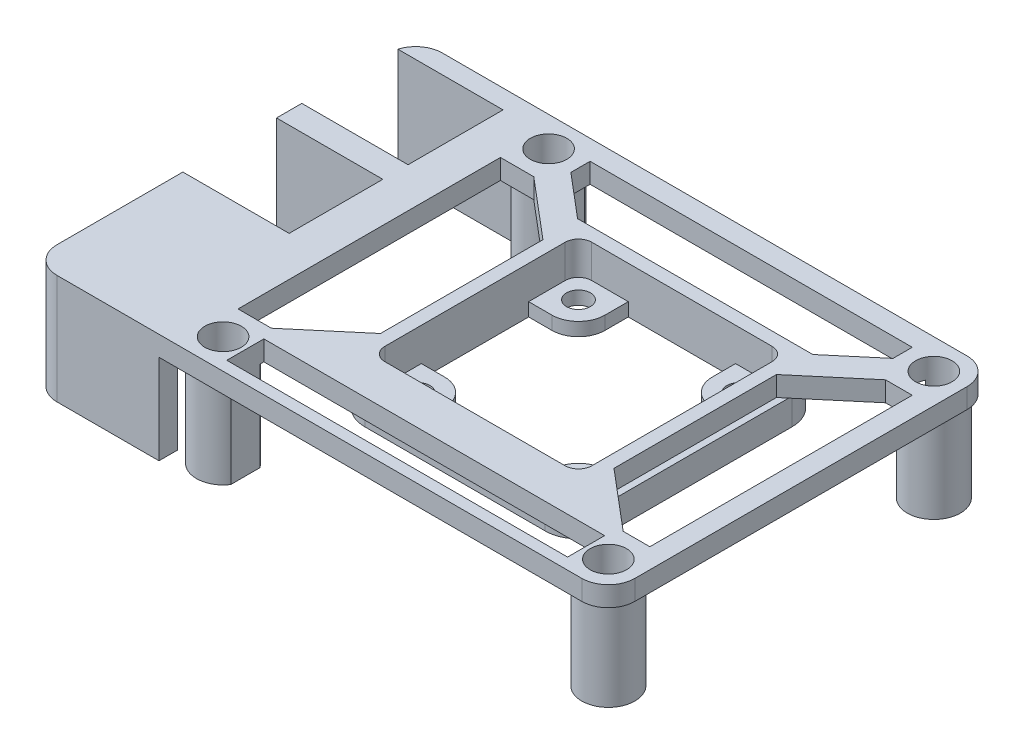
SolidWorks part; units mm, degrees
ref_plane "Front Plane" through (0, 0, 0) normal (0, 0, 1) x (1, 0, 0)
ref_plane "Top Plane" through (0, 0, 0) normal (0, 1, 0) x (1, 0, 0)
ref_plane "Right Plane" through (0, 0, 0) normal (1, 0, 0) x (0, 0, -1)
sketch "Sketch1" plane through (0, -22.49, 0) normal (0, 1, 0) x (1, 0, 0)
  circle A0 centre (42.46, 15.03) radius 4
  circle A1 centre (-15.54, 15.03) radius 4
  circle A2 centre (-15.54, -33.97) radius 4
  circle A3 centre (42.46, -33.97) radius 4
  dimension "D1" = 8
extrude "Boss-Extrude1" add sketch "Sketch1" along normal blind 16.5
sketch "Sketch2" plane through (0, -5.99, 0) normal (0, 1, 0) x (1, 0, 0)
  line L4 (-36.04, -37.47) -> (42.96, -37.47)
  line L5 (45.96, -34.47) -> (45.96, 15.53)
  line L6 (42.96, 18.53) -> (-36.04, 18.53)
  line L7 (-39.04, 15.53) -> (-39.04, -34.47)
  line L8 (-36.04, -37.47) -> (42.96, -37.47) construction
  line L9 (45.96, -34.47) -> (45.96, 15.53) construction
  line L10 (42.96, 18.53) -> (-36.04, 18.53) construction
  line L11 (-39.04, 15.53) -> (-39.04, -34.47) construction
  line L24 (-36.04, -38.47) -> (42.96, -38.47)
  line L25 (46.96, -34.47) -> (46.96, 15.53)
  line L26 (42.96, 19.53) -> (-36.04, 19.53)
  line L27 (-40.04, 15.53) -> (-40.04, -34.47)
  circle A1 centre (42.46, 15.03) radius 1.35
  circle A2 centre (42.46, 15.03) radius 1.35
  circle A3 centre (-15.54, 15.03) radius 1.35
  circle A4 centre (-15.54, 15.03) radius 1.35
  circle A5 centre (-15.54, -33.97) radius 1.35
  circle A6 centre (-15.54, -33.97) radius 1.35
  circle A7 centre (42.46, -33.97) radius 1.35
  circle A8 centre (42.46, -33.97) radius 1.35
  arc A12 (-39.04, -34.47) -> (-36.04, -37.47) centre (-36.04, -34.47) ccw
  arc A13 (42.96, -37.47) -> (45.96, -34.47) centre (42.96, -34.47) ccw
  arc A14 (45.96, 15.53) -> (42.96, 18.53) centre (42.96, 15.53) ccw
  arc A15 (-36.04, 18.53) -> (-39.04, 15.53) centre (-36.04, 15.53) ccw
  arc A16 (-39.04, -34.47) -> (-36.04, -37.47) centre (-36.04, -34.47) ccw construction
  arc A17 (42.96, -37.47) -> (45.96, -34.47) centre (42.96, -34.47) ccw construction
  arc A18 (45.96, 15.53) -> (42.96, 18.53) centre (42.96, 15.53) ccw construction
  arc A19 (-36.04, 18.53) -> (-39.04, 15.53) centre (-36.04, 15.53) ccw construction
  arc A48 (-40.04, -34.47) -> (-36.04, -38.47) centre (-36.04, -34.47) ccw
  arc A49 (42.96, -38.47) -> (46.96, -34.47) centre (42.96, -34.47) ccw
  arc A50 (46.96, 15.53) -> (42.96, 19.53) centre (42.96, 15.53) ccw
  arc A51 (-36.04, 19.53) -> (-40.04, 15.53) centre (-36.04, 15.53) ccw
  dimension "D1" = 0
  dimension "D2" = 0
  dimension "D3" = 0
  dimension "D4" = 0
  dimension "D5" = 0
  dimension "D6" = 1
extrude "Boss-Extrude2" add sketch "Sketch2" against normal blind 3
sketch "Sketch3" plane through (0, -8.99, 0) normal (0, -1, 0) x (1, 0, 0)
  line L1 (-40.04, -15.53) -> (-40.04, 34.47)
  line L2 (-36.04, 38.47) -> (-20.69, 38.47)
  line L4 (-20.69, 38.47) -> (-20.69, -19.53)
  line L6 (-20.69, -19.53) -> (-36.04, -19.53)
  line L9 (-20.69, 34.97) -> (-20.69, 19.47) construction
  line L11 (42.96, -19.53) -> (-36.04, -19.53) construction
  line L13 (-36.04, 38.47) -> (42.96, 38.47) construction
  line L14 (-40.04, -15.53) -> (-40.04, 34.47) construction
  arc A2 (-40.04, -15.53) -> (-36.04, -19.53) centre (-36.04, -15.53) ccw
  arc A3 (-36.04, 38.47) -> (-40.04, 34.47) centre (-36.04, 34.47) ccw
  arc A6 (-40.04, -15.53) -> (-36.04, -19.53) centre (-36.04, -15.53) ccw construction
  arc A7 (-36.04, 38.47) -> (-40.04, 34.47) centre (-36.04, 34.47) ccw construction
extrude "Boss-Extrude3" add sketch "Sketch3" along normal up to surface (13.5 mm away) up to face at (-19.54, -22.49, 33.97)
sketch "Sketch4" plane through (0, -5.99, 0) normal (0, 1, 0) x (1, 0, 0)
  line L1 (25.535, -21.545) -> (1.385, -21.545)
  line L2 (25.535, -21.545) -> (25.535, 2.605)
  line L3 (25.535, 2.605) -> (1.385, 2.605)
  line L4 (1.385, -21.545) -> (1.385, 2.605)
sketch "Sketch5" plane through (0, -5.99, 0) normal (0, 1, 0) x (1, 0, 0)
  line L0 (25.535, -21.545) -> (1.385, -21.545) construction
  line L1 (1.385, 2.605) -> (25.535, 2.605)
  line L2 (1.385, 2.605) -> (1.385, -21.545)
  line L3 (1.385, -21.545) -> (25.535, -21.545)
  line L4 (25.535, 2.605) -> (25.535, -21.545)
  line L5 (25.535, -21.545) -> (25.535, 2.605) construction
  line L6 (22.21, -13.97) -> (11.21, -13.97) construction
  line L7 (11.21, -8.67) -> (11.21, -19.27) construction
  line L8 (22.21, -19.27) -> (22.21, -8.67) construction
  line L9 (25.535, 2.605) -> (1.385, -21.545) construction
  line L10 (-15.54, 15.03) -> (42.46, -33.97) construction
  line L11 (-15.54, -33.97) -> (42.46, 15.03) construction
  point P10 (16.71, -13.97)
  point P23 (13.46, -9.47)
  point P24 (0, 0)
sketch "Sketch8" plane through (0, -5.99, 0) normal (0, 1, 0) x (1, 0, 0)
  line L8 (29.035, 6.105) -> (-2.115, 6.105)
  line L9 (29.035, -25.045) -> (29.035, 6.105)
  line L10 (-2.115, -25.045) -> (29.035, -25.045)
  line L11 (-2.115, 6.105) -> (-2.115, -25.045)
  line L12 (27.035, 6.105) -> (-0.115, 6.105)
  line L13 (29.035, -23.045) -> (29.035, 4.105)
  line L14 (-0.115, -25.045) -> (27.035, -25.045)
  line L15 (-2.115, 4.105) -> (-2.115, -23.045)
  arc A0 (27.035, 6.105) -> (29.035, 4.105) centre (27.035, 4.105) cw
  arc A1 (-0.115, 6.105) -> (-2.115, 4.105) centre (-0.115, 4.105) ccw
  arc A2 (-0.115, -25.045) -> (-2.115, -23.045) centre (-0.115, -23.045) cw
  arc A3 (29.035, -23.045) -> (27.035, -25.045) centre (27.035, -23.045) cw
  dimension "D2" = 2
  dimension "D1" = 3.5
extrude "Cut-Extrude1" cut sketch "Sketch8" against normal through all
sketch "Sketch9" plane through (0, -8.99, 0) normal (0, -1, 0) x (1, 0, 0)
  line L4 (-0.115, -6.105) -> (27.035, -6.105)
  line L5 (-2.115, 23.045) -> (-2.115, -4.105)
  line L6 (27.035, 25.045) -> (-0.115, 25.045)
  line L7 (29.035, -4.105) -> (29.035, 23.045)
  line L8 (-0.115, -6.105) -> (27.035, -6.105)
  line L9 (-2.115, 23.045) -> (-2.115, -4.105)
  line L10 (27.035, 25.045) -> (-0.115, 25.045)
  line L11 (29.035, -4.105) -> (29.035, 23.045)
  line L12 (32.035, -4.105) -> (32.035, 23.045)
  line L13 (27.035, 28.045) -> (-0.115, 28.045)
  line L14 (-5.115, 23.045) -> (-5.115, -4.105)
  line L15 (-0.115, -9.105) -> (27.035, -9.105)
  arc A4 (-2.115, -4.105) -> (-0.115, -6.105) centre (-0.115, -4.105) ccw
  arc A5 (-0.115, 25.045) -> (-2.115, 23.045) centre (-0.115, 23.045) ccw
  arc A6 (29.035, 23.045) -> (27.035, 25.045) centre (27.035, 23.045) ccw
  arc A7 (27.035, -6.105) -> (29.035, -4.105) centre (27.035, -4.105) ccw
  arc A8 (-2.115, -4.105) -> (-0.115, -6.105) centre (-0.115, -4.105) ccw
  arc A9 (-0.115, 25.045) -> (-2.115, 23.045) centre (-0.115, 23.045) ccw
  arc A10 (29.035, 23.045) -> (27.035, 25.045) centre (27.035, 23.045) ccw
  arc A11 (27.035, -6.105) -> (29.035, -4.105) centre (27.035, -4.105) ccw
  arc A12 (32.035, 23.045) -> (27.035, 28.045) centre (27.035, 23.045) ccw
  arc A13 (-0.115, 28.045) -> (-5.115, 23.045) centre (-0.115, 23.045) ccw
  arc A14 (-5.115, -4.105) -> (-0.115, -9.105) centre (-0.115, -4.105) ccw
  arc A15 (27.035, -9.105) -> (32.035, -4.105) centre (27.035, -4.105) ccw
  dimension "D1" = 0
  dimension "D3" = 3
extrude "Boss-Extrude4" add sketch "Sketch9" along normal offset from surface (4 mm away) 2 offset beyond the face yes
sketch "Sketch10" plane through (0, -12.99, 0) normal (0, -1, 0) x (1, 0, 0)
  line L0 (29.035, 17.545) -> (25.535, 17.545)
  line L1 (29.035, 23.045) -> (29.035, -4.105) construction
  line L2 (21.535, 21.545) -> (21.535, 25.045)
  line L3 (-0.115, 25.045) -> (27.035, 25.045) construction
  line L4 (27.035, -6.105) -> (-0.115, -6.105) construction
  line L5 (-2.115, -4.105) -> (-2.115, 23.045) construction
  line L6 (27.035, -6.105) -> (21.535, -6.105)
  line L7 (-2.115, -4.105) -> (-2.115, 1.395)
  line L8 (-0.115, 25.045) -> (5.385, 25.045)
  line L9 (29.035, 23.045) -> (29.035, 17.545)
  line L10 (5.385, 21.545) -> (5.385, 25.045)
  line L11 (1.385, 17.545) -> (-2.115, 17.545)
  line L12 (1.385, 1.395) -> (-2.115, 1.395)
  line L13 (5.385, -2.605) -> (5.385, -6.105)
  line L14 (25.535, 1.395) -> (29.035, 1.395)
  line L15 (21.535, -2.605) -> (21.535, -6.105)
  line L16 (-2.115, 17.545) -> (-2.115, 23.045)
  line L17 (5.385, -6.105) -> (-0.115, -6.105)
  line L18 (29.035, 1.395) -> (29.035, -4.105)
  line L19 (21.535, 25.045) -> (27.035, 25.045)
  arc A0 (21.535, 21.545) -> (25.535, 17.545) centre (25.535, 21.545) ccw
  arc A1 (1.385, 17.545) -> (5.385, 21.545) centre (1.385, 21.545) ccw
  arc A2 (5.385, -2.605) -> (1.385, 1.395) centre (1.385, -2.605) ccw
  arc A3 (25.535, 1.395) -> (21.535, -2.605) centre (25.535, -2.605) ccw
  arc A4 (27.035, -6.105) -> (29.035, -4.105) centre (27.035, -4.105) ccw construction
  arc A5 (-2.115, -4.105) -> (-0.115, -6.105) centre (-0.115, -4.105) ccw construction
  arc A6 (-0.115, 25.045) -> (-2.115, 23.045) centre (-0.115, 23.045) ccw construction
  arc A7 (29.035, 23.045) -> (27.035, 25.045) centre (27.035, 23.045) ccw construction
  arc A8 (27.035, -6.105) -> (29.035, -4.105) centre (27.035, -4.105) ccw
  arc A9 (-2.115, -4.105) -> (-0.115, -6.105) centre (-0.115, -4.105) ccw
  arc A10 (-0.115, 25.045) -> (-2.115, 23.045) centre (-0.115, 23.045) ccw
  arc A11 (29.035, 23.045) -> (27.035, 25.045) centre (27.035, 23.045) ccw
  dimension "D1" = 4
extrude "Boss-Extrude5" add sketch "Sketch10" against normal up to surface (2 mm away)
hole_wizard "M3 Clearance Hole1" positions "Sketch6" profile "Sketch7" hole size "M3" standard "ANSI Metric" end condition through all
sketch "Sketch6" plane through (0, -5.99, 0) normal (0, 1, 0) x (1, 0, 0)
  point P0 (25.535, -21.545)
  point P3 (1.385, -21.545)
  point P6 (1.385, 2.605)
  point P9 (25.535, 2.605)
sketch "Sketch7" plane through (25.535, -5.99, 21.545) normal (1, 0, 0) x (0, 0, 1)
  line L0 (0, 0) -> (0, 16.5)
  line L1 (0, 16.5) -> (1.8, 16.5)
  line L2 (1.8, 16.5) -> (1.8, 0)
  line L5 (1.8, 0) -> (0, 0)
  line L11 (0, -6.35) -> (0, 107.95) construction
  dimension "Thru Hole Dia." = 3.6
  dimension "Thru Hole Depth" = 16.5
sketch "Sketch11" plane through (0, -5.99, 0) normal (0, 1, 0) x (1, 0, 0)
  line L0 (-12.19, -36.76) -> (39.11, -36.76)
  line L1 (39.11, -36.76) -> (39.11, -31.18)
  line L2 (39.11, -31.18) -> (-12.19, -31.18)
  line L3 (-12.19, -31.18) -> (-12.19, -36.76)
  line L4 (-11.94, -36.51) -> (38.86, -36.51)
  line L5 (38.86, -36.51) -> (38.86, -31.43)
  line L6 (38.86, -31.43) -> (-11.94, -31.43)
  line L7 (-11.94, -31.43) -> (-11.94, -36.51)
  line L8 (-11.94, -36.51) -> (38.86, -36.51) construction
  line L9 (38.86, -36.51) -> (38.86, -31.43) construction
  line L10 (38.86, -31.43) -> (-11.94, -31.43) construction
  line L11 (-11.94, -31.43) -> (-11.94, -36.51) construction
  dimension "D1" = 0
  dimension "D2" = 0.25
extrude "Cut-Extrude2" cut sketch "Sketch11" against normal through all
sketch "Sketch12" plane through (-40.04, 0, 0) normal (-1, 0, 0) x (0, 0, 1)
  line L28 (1.42, -24.59) -> (15.52, -24.59)
  line L29 (15.52, -24.59) -> (15.52, -6.49)
  line L30 (15.52, -6.49) -> (1.42, -6.49) construction
  line L31 (1.42, -6.49) -> (1.42, -24.59)
  line L32 (1.92, -24.09) -> (15.02, -24.09)
  line L33 (15.02, -24.09) -> (15.02, -6.99)
  line L34 (15.02, -6.99) -> (1.92, -6.99)
  line L35 (1.92, -6.99) -> (1.92, -24.09)
  line L36 (1.92, -24.09) -> (15.02, -24.09) construction
  line L37 (15.02, -24.09) -> (15.02, -6.99) construction
  line L38 (15.02, -6.99) -> (1.92, -6.99) construction
  line L39 (1.92, -6.99) -> (1.92, -24.09) construction
  line L40 (-16.18, -24.09) -> (-2.88, -24.09)
  line L41 (-2.88, -24.09) -> (-2.88, -6.99)
  line L42 (-2.88, -6.99) -> (-16.18, -6.99)
  line L43 (-16.18, -6.99) -> (-16.18, -24.09)
  line L44 (-16.18, -24.09) -> (-2.88, -24.09) construction
  line L45 (-2.88, -24.09) -> (-2.88, -6.99) construction
  line L46 (-2.88, -6.99) -> (-16.18, -6.99) construction
  line L47 (-16.18, -6.99) -> (-16.18, -24.09) construction
  line L48 (19.27, -9.19) -> (19.27, -24.09)
  line L49 (34.97, -8.99) -> (19.47, -8.99)
  line L50 (35.17, -24.09) -> (35.17, -9.19)
  line L51 (19.27, -24.09) -> (35.17, -24.09)
  line L52 (19.27, -9.19) -> (19.27, -24.09) construction
  line L53 (34.97, -8.99) -> (19.47, -8.99) construction
  line L54 (35.17, -24.09) -> (35.17, -9.19) construction
  line L55 (19.27, -24.09) -> (35.17, -24.09) construction
  line L56 (-16.68, -24.59) -> (-2.38, -24.59)
  line L57 (-2.38, -24.59) -> (-2.38, -6.49)
  line L58 (-2.38, -6.49) -> (-16.68, -6.49) construction
  line L59 (-16.68, -6.49) -> (-16.68, -24.59)
  line L60 (18.77, -9.19) -> (18.77, -24.59)
  line L61 (18.77, -24.59) -> (35.67, -24.59)
  line L62 (35.67, -24.59) -> (35.67, -9.19)
  line L63 (34.97, -8.49) -> (19.47, -8.49)
  line L64 (-16.68, -6.49) -> (-16.68, -5.99)
  line L66 (-16.68, -5.99) -> (-2.38, -5.99)
  line L68 (-2.38, -5.99) -> (-2.38, -6.49)
  line L69 (1.42, -6.49) -> (1.42, -5.99)
  line L70 (1.42, -5.99) -> (15.52, -5.99)
  line L71 (-2.605, -5.99) -> (21.545, -5.99) construction
  line L72 (15.52, -5.99) -> (15.52, -6.49)
  line L88 (-15.53, -5.99) -> (34.47, -5.99) construction
  arc A0 (35.67, -9.19) -> (34.97, -8.49) centre (34.97, -9.19) ccw
  arc A1 (19.47, -8.49) -> (18.77, -9.19) centre (19.47, -9.19) ccw
  arc A2 (19.47, -8.99) -> (19.27, -9.19) centre (19.47, -9.19) ccw
  arc A3 (35.17, -9.19) -> (34.97, -8.99) centre (34.97, -9.19) ccw
  arc A4 (19.47, -8.99) -> (19.27, -9.19) centre (19.47, -9.19) ccw construction
  arc A5 (35.17, -9.19) -> (34.97, -8.99) centre (34.97, -9.19) ccw construction
  dimension "D1" = 0
  dimension "D2" = 0
  dimension "D3" = 0
  dimension "D4" = 0.5
extrude "Cut-Extrude3" cut sketch "Sketch12" against normal blind 16 contours L59 L56 L57 L68 L66 L64 | L31 L28 L29 L72 L70 L69
extrude "Cut-Extrude4" cut sketch "Sketch12<3>" against normal blind 20 contours L60 L61 L62 A0 L63 A1
sketch "Sketch12<3>" plane through (-40.04, 0, 0) normal (-1, 0, 0) x (0, 0, 1) same geometry as "Sketch12"
sketch "Sketch13" plane through (-20.69, 0, 0) normal (1, 0, 0) x (0, 0, -1)
  line L4 (19.53, -8.99) -> (-18.7992, -8.99)
  line L5 (-18.77, -9.19) -> (-18.77, -22.49)
  line L6 (-18.77, -22.49) -> (19.53, -22.49)
  line L10 (-18.77, -22.49) -> (19.53, -22.49)
  line L15 (-18.77, -9.19) -> (-18.77, -22.49)
  line L17 (19.53, -22.49) -> (19.53, -8.99)
  line L18 (19.53, -22.49) -> (19.53, -8.99)
  line L19 (19.53, -8.99) -> (-18.7992, -8.99)
  arc A1 (-18.77, -9.19) -> (-18.7992, -8.99) centre (-19.47, -9.19) ccw
  arc A4 (-18.77, -9.19) -> (-18.7992, -8.99) centre (-19.47, -9.19) ccw
  dimension "D1" = 0
extrude "Cut-Extrude5" cut sketch "Sketch13" against normal offset from surface (1.35 mm away) 2 up to face at (-24.04, -14.24, -9.53)
sketch "Sketch15" plane through (0, 0, 18.77) normal (0, 0, 1) x (1, 0, 0)
  line L0 (-37.04, -22.49) -> (-22.04, -12.19)
  line L1 (-22.04, -22.49) -> (-40.04, -22.49) construction
  line L2 (-22.04, -22.49) -> (-22.04, -9.19) construction
  line L3 (-22.04, -12.19) -> (-22.04, -22.49)
  line L4 (-22.04, -22.49) -> (-37.04, -22.49)
  line L5 (-40.04, -22.49) -> (-37.04, -22.49) construction
  line L6 (-22.04, -12.19) -> (-22.04, -9.19) construction
  dimension "D1" = 3
extrude "Cut-Extrude6" cut sketch "Sketch15" against normal up to surface (35.45 mm away) up to face at (-31.9556, -14.24, -16.68)
hole_wizard "CBORE for M2.5 SHCS1" positions "Sketch16" profile "Sketch17" counterbore size "M2.5" standard "ANSI Metric" end condition through all
sketch "Sketch16" plane through (0, -5.99, 0) normal (0, 1, 0) x (1, 0, 0)
  point P0 (-15.54, -33.97)
  point P3 (-15.54, 15.03)
  point P6 (42.46, 15.03)
  point P9 (42.46, -33.97)
sketch "Sketch17" plane through (-15.54, -5.99, 33.97) normal (1, 0, 0) x (0, 0, 1)
  line L0 (0, 0) -> (0, 16.5)
  line L1 (0, 16.5) -> (1.45, 16.5)
  line L3 (1.45, 16.5) -> (1.45, 2.5)
  line L4 (1.45, 2.5) -> (2.75, 2.5)
  line L5 (2.75, 2.5) -> (2.75, 0)
  line L7 (2.75, 0) -> (0, 0)
  line L11 (0, -6.35) -> (0, 107.95) construction
  dimension "Thru Hole Dia." = 2.9
  dimension "Thru Hole Depth" = 16.5
  dimension "C'Bore Dia." = 5.5
  dimension "C'Bore Depth" = 2.5
sketch "Sketch18" plane through (0, -8.49, 0) normal (0, 1, 0) x (1, 0, 0)
  circle A0 centre (-15.54, 15.03) radius 2.75 construction
  circle A1 centre (42.46, 15.03) radius 2.75
  circle A2 centre (42.46, 15.03) radius 2.75
  circle A3 centre (-15.54, -33.97) radius 2.75 construction
  circle A4 centre (42.46, -33.97) radius 2.75 construction
  circle A5 centre (-15.54, 15.03) radius 2.75
  circle A6 centre (-15.54, -33.97) radius 2.75
  circle A7 centre (42.46, -33.97) radius 2.75
  dimension "D1" = 0
extrude "Cut-Extrude7" cut sketch "Sketch18" against normal offset from surface (8.6 mm away) 7
sketch "Sketch19" plane through (0, -8.99, 0) normal (0, -1, 0) x (-1, 0, 0)
  line L0 (-42.96, 19.53) -> (22.04, 19.53) construction
  line L1 (-39.98, 19.53) -> (12.04, 19.53)
  line L2 (-39.98, 19.53) -> (-39.98, 9.53)
  line L3 (-39.98, 9.53) -> (12.04, 9.53)
  line L4 (12.04, 19.53) -> (12.04, 9.53)
  line L5 (11.04, 18.53) -> (5.04, 18.53) construction
  line L6 (11.04, 18.53) -> (5.04, 18.53) construction
  line L7 (-37.93, 18.53) -> (-39.23, 18.53) construction
  line L8 (-37.93, 18.53) -> (-39.23, 18.53) construction
  dimension "D1" = 10
  dimension "D2" = 1
  dimension "D3" = 0.75
extrude "Cut-Extrude8" cut sketch "Sketch19" along normal through all
sketch "Sketch20" [suppressed] plane through (0, -5.99, 0) normal (0, 1, 0) x (1, 0, 0)
  line L0 (-15.54, 11.5659) -> (-13.54, 15.03) construction
  line L1 (-13.54, 15.03) -> (-9.54, 15.03) construction
  line L2 (-9.54, 15.03) -> (-11.54, 11.5659) construction
  line L3 (-11.54, 11.5659) -> (-15.54, 11.5659) construction
  line L4 (-15.54, 11.5659) -> (-15.54, 15.03) construction
  line L5 (-15.54, 15.03) -> (-13.54, 15.03) construction
  circle A0 centre (-13.54, 15.03) radius 1.5
  circle A1 centre (-9.54, 15.03) radius 1.5
  circle A2 centre (-15.54, 11.5659) radius 1.5
  circle A3 centre (-11.54, 11.5659) radius 1.5
  point P9 (-15.54, 15.03)
  dimension "D1" = 60
  dimension "D2" = 3
  dimension "D3" = 4
sketch "Sketch21" [suppressed] plane through (0, -5.99, 0) normal (0, 1, 0) x (1, 0, 0)
  line L0 (-9.54, 15.03) -> (-5.54, 15.03) construction
  line L1 (-11.54, 11.5659) -> (-13.54, 8.1018) construction
  line L2 (-9.54, 15.03) -> (-11.54, 11.5659) construction
  line L3 (-13.54, 15.03) -> (-9.54, 15.03) construction
  circle A0 centre (-3.54, 11.5659) radius 1.5
  circle A1 centre (-11.54, 11.5659) radius 1.5
  circle A2 centre (-11.54, 11.5659) radius 1.5
  circle A3 centre (-15.54, 11.5659) radius 1.5
  circle A4 centre (-15.54, 11.5659) radius 1.5
  circle A5 centre (-9.54, 15.03) radius 1.5
  circle A6 centre (-9.54, 15.03) radius 1.5
  circle A7 centre (-13.54, 15.03) radius 1.5
  circle A8 centre (-13.54, 15.03) radius 1.5
  circle A9 centre (-7.54, 11.5659) radius 1.5
  circle A10 centre (-1.54, 15.03) radius 1.5
  circle A11 centre (-5.54, 15.03) radius 1.5
  circle A12 centre (4.46, 11.5659) radius 1.5
  circle A13 centre (0.46, 11.5659) radius 1.5
  circle A14 centre (6.46, 15.03) radius 1.5
  circle A15 centre (2.46, 15.03) radius 1.5
  circle A16 centre (12.46, 11.5659) radius 1.5
  circle A17 centre (8.46, 11.5659) radius 1.5
  circle A18 centre (14.46, 15.03) radius 1.5
  circle A19 centre (10.46, 15.03) radius 1.5
  circle A20 centre (20.46, 11.5659) radius 1.5
  circle A21 centre (16.46, 11.5659) radius 1.5
  circle A22 centre (22.46, 15.03) radius 1.5
  circle A23 centre (18.46, 15.03) radius 1.5
  circle A24 centre (28.46, 11.5659) radius 1.5
  circle A25 centre (24.46, 11.5659) radius 1.5
  circle A26 centre (30.46, 15.03) radius 1.5
  circle A27 centre (26.46, 15.03) radius 1.5
  circle A28 centre (36.46, 11.5659) radius 1.5
  circle A29 centre (32.46, 11.5659) radius 1.5
  circle A30 centre (38.46, 15.03) radius 1.5
  circle A31 centre (34.46, 15.03) radius 1.5
  circle A32 centre (44.46, 11.5659) radius 1.5
  circle A33 centre (40.46, 11.5659) radius 1.5
  circle A34 centre (46.46, 15.03) radius 1.5
  circle A35 centre (42.46, 15.03) radius 1.5
  circle A36 centre (-3.54, 4.6377) radius 1.5
  circle A37 centre (-7.54, 4.6377) radius 1.5
  circle A38 centre (-1.54, 8.1018) radius 1.5
  circle A39 centre (-5.54, 8.1018) radius 1.5
  circle A40 centre (4.46, 4.6377) radius 1.5
  circle A41 centre (0.46, 4.6377) radius 1.5
  circle A42 centre (6.46, 8.1018) radius 1.5
  circle A43 centre (2.46, 8.1018) radius 1.5
  circle A44 centre (12.46, 4.6377) radius 1.5
  circle A45 centre (8.46, 4.6377) radius 1.5
  circle A46 centre (14.46, 8.1018) radius 1.5
  circle A47 centre (10.46, 8.1018) radius 1.5
  circle A48 centre (20.46, 4.6377) radius 1.5
  circle A49 centre (16.46, 4.6377) radius 1.5
  circle A50 centre (22.46, 8.1018) radius 1.5
  circle A51 centre (18.46, 8.1018) radius 1.5
  circle A52 centre (28.46, 4.6377) radius 1.5
  circle A53 centre (24.46, 4.6377) radius 1.5
  circle A54 centre (30.46, 8.1018) radius 1.5
  circle A55 centre (26.46, 8.1018) radius 1.5
  circle A56 centre (36.46, 4.6377) radius 1.5
  circle A57 centre (32.46, 4.6377) radius 1.5
  circle A58 centre (38.46, 8.1018) radius 1.5
  circle A59 centre (34.46, 8.1018) radius 1.5
  circle A60 centre (44.46, 4.6377) radius 1.5
  circle A61 centre (40.46, 4.6377) radius 1.5
  circle A62 centre (46.46, 8.1018) radius 1.5
  circle A63 centre (42.46, 8.1018) radius 1.5
  circle A64 centre (-3.54, -2.2905) radius 1.5
  circle A65 centre (-7.54, -2.2905) radius 1.5
  circle A66 centre (-1.54, 1.1736) radius 1.5
  circle A67 centre (-5.54, 1.1736) radius 1.5
  circle A68 centre (4.46, -2.2905) radius 1.5
  circle A69 centre (0.46, -2.2905) radius 1.5
  circle A70 centre (6.46, 1.1736) radius 1.5
  circle A71 centre (2.46, 1.1736) radius 1.5
  circle A72 centre (12.46, -2.2905) radius 1.5
  circle A73 centre (8.46, -2.2905) radius 1.5
  circle A74 centre (14.46, 1.1736) radius 1.5
  circle A75 centre (10.46, 1.1736) radius 1.5
  circle A76 centre (20.46, -2.2905) radius 1.5
  circle A77 centre (16.46, -2.2905) radius 1.5
  circle A78 centre (22.46, 1.1736) radius 1.5
  circle A79 centre (18.46, 1.1736) radius 1.5
  circle A80 centre (28.46, -2.2905) radius 1.5
  circle A81 centre (24.46, -2.2905) radius 1.5
  circle A82 centre (30.46, 1.1736) radius 1.5
  circle A83 centre (26.46, 1.1736) radius 1.5
  circle A84 centre (36.46, -2.2905) radius 1.5
  circle A85 centre (32.46, -2.2905) radius 1.5
  circle A86 centre (38.46, 1.1736) radius 1.5
  circle A87 centre (34.46, 1.1736) radius 1.5
  circle A88 centre (44.46, -2.2905) radius 1.5
  circle A89 centre (40.46, -2.2905) radius 1.5
  circle A90 centre (46.46, 1.1736) radius 1.5
  circle A91 centre (42.46, 1.1736) radius 1.5
  circle A92 centre (-3.54, -9.2187) radius 1.5
  circle A93 centre (-7.54, -9.2187) radius 1.5
  circle A94 centre (-1.54, -5.7546) radius 1.5
  circle A95 centre (-5.54, -5.7546) radius 1.5
  circle A96 centre (4.46, -9.2187) radius 1.5
  circle A97 centre (0.46, -9.2187) radius 1.5
  circle A98 centre (6.46, -5.7546) radius 1.5
  circle A99 centre (2.46, -5.7546) radius 1.5
  circle A100 centre (12.46, -9.2187) radius 1.5
  circle A101 centre (8.46, -9.2187) radius 1.5
  circle A102 centre (14.46, -5.7546) radius 1.5
  circle A103 centre (10.46, -5.7546) radius 1.5
  circle A104 centre (20.46, -9.2187) radius 1.5
  circle A105 centre (16.46, -9.2187) radius 1.5
  circle A106 centre (22.46, -5.7546) radius 1.5
  circle A107 centre (18.46, -5.7546) radius 1.5
  circle A108 centre (28.46, -9.2187) radius 1.5
  circle A109 centre (24.46, -9.2187) radius 1.5
  circle A110 centre (30.46, -5.7546) radius 1.5
  circle A111 centre (26.46, -5.7546) radius 1.5
  circle A112 centre (36.46, -9.2187) radius 1.5
  circle A113 centre (32.46, -9.2187) radius 1.5
  circle A114 centre (38.46, -5.7546) radius 1.5
  circle A115 centre (34.46, -5.7546) radius 1.5
  circle A116 centre (44.46, -9.2187) radius 1.5
  circle A117 centre (40.46, -9.2187) radius 1.5
  circle A118 centre (46.46, -5.7546) radius 1.5
  circle A119 centre (42.46, -5.7546) radius 1.5
  circle A120 centre (-3.54, -16.1469) radius 1.5
  circle A121 centre (-7.54, -16.1469) radius 1.5
  circle A122 centre (-1.54, -12.6828) radius 1.5
  circle A123 centre (-5.54, -12.6828) radius 1.5
  circle A124 centre (4.46, -16.1469) radius 1.5
  circle A125 centre (0.46, -16.1469) radius 1.5
  circle A126 centre (6.46, -12.6828) radius 1.5
  circle A127 centre (2.46, -12.6828) radius 1.5
  circle A128 centre (12.46, -16.1469) radius 1.5
  circle A129 centre (8.46, -16.1469) radius 1.5
  circle A130 centre (14.46, -12.6828) radius 1.5
  circle A131 centre (10.46, -12.6828) radius 1.5
  circle A132 centre (20.46, -16.1469) radius 1.5
  circle A133 centre (16.46, -16.1469) radius 1.5
  circle A134 centre (22.46, -12.6828) radius 1.5
  circle A135 centre (18.46, -12.6828) radius 1.5
  circle A136 centre (28.46, -16.1469) radius 1.5
  circle A137 centre (24.46, -16.1469) radius 1.5
  circle A138 centre (30.46, -12.6828) radius 1.5
  circle A139 centre (26.46, -12.6828) radius 1.5
  circle A140 centre (36.46, -16.1469) radius 1.5
  circle A141 centre (32.46, -16.1469) radius 1.5
  circle A142 centre (38.46, -12.6828) radius 1.5
  circle A143 centre (34.46, -12.6828) radius 1.5
  circle A144 centre (44.46, -16.1469) radius 1.5
  circle A145 centre (40.46, -16.1469) radius 1.5
  circle A146 centre (46.46, -12.6828) radius 1.5
  circle A147 centre (42.46, -12.6828) radius 1.5
  circle A148 centre (-3.54, -23.0751) radius 1.5
  circle A149 centre (-7.54, -23.0751) radius 1.5
  circle A150 centre (-1.54, -19.611) radius 1.5
  circle A151 centre (-5.54, -19.611) radius 1.5
  circle A152 centre (4.46, -23.0751) radius 1.5
  circle A153 centre (0.46, -23.0751) radius 1.5
  circle A154 centre (6.46, -19.611) radius 1.5
  circle A155 centre (2.46, -19.611) radius 1.5
  circle A156 centre (12.46, -23.0751) radius 1.5
  circle A157 centre (8.46, -23.0751) radius 1.5
  circle A158 centre (14.46, -19.611) radius 1.5
  circle A159 centre (10.46, -19.611) radius 1.5
  circle A160 centre (20.46, -23.0751) radius 1.5
  circle A161 centre (16.46, -23.0751) radius 1.5
  circle A162 centre (22.46, -19.611) radius 1.5
  circle A163 centre (18.46, -19.611) radius 1.5
  circle A164 centre (28.46, -23.0751) radius 1.5
  circle A165 centre (24.46, -23.0751) radius 1.5
  circle A166 centre (30.46, -19.611) radius 1.5
  circle A167 centre (26.46, -19.611) radius 1.5
  circle A168 centre (36.46, -23.0751) radius 1.5
  circle A169 centre (32.46, -23.0751) radius 1.5
  circle A170 centre (38.46, -19.611) radius 1.5
  circle A171 centre (34.46, -19.611) radius 1.5
  circle A172 centre (44.46, -23.0751) radius 1.5
  circle A173 centre (40.46, -23.0751) radius 1.5
  circle A174 centre (46.46, -19.611) radius 1.5
  circle A175 centre (42.46, -19.611) radius 1.5
  circle A176 centre (-3.54, -30.0033) radius 1.5
  circle A177 centre (-7.54, -30.0033) radius 1.5
  circle A178 centre (-1.54, -26.5392) radius 1.5
  circle A179 centre (-5.54, -26.5392) radius 1.5
  circle A180 centre (4.46, -30.0033) radius 1.5
  circle A181 centre (0.46, -30.0033) radius 1.5
  circle A182 centre (6.46, -26.5392) radius 1.5
  circle A183 centre (2.46, -26.5392) radius 1.5
  circle A184 centre (12.46, -30.0033) radius 1.5
  circle A185 centre (8.46, -30.0033) radius 1.5
  circle A186 centre (14.46, -26.5392) radius 1.5
  circle A187 centre (10.46, -26.5392) radius 1.5
  circle A188 centre (20.46, -30.0033) radius 1.5
  circle A189 centre (16.46, -30.0033) radius 1.5
  circle A190 centre (22.46, -26.5392) radius 1.5
  circle A191 centre (18.46, -26.5392) radius 1.5
  circle A192 centre (28.46, -30.0033) radius 1.5
  circle A193 centre (24.46, -30.0033) radius 1.5
  circle A194 centre (30.46, -26.5392) radius 1.5
  circle A195 centre (26.46, -26.5392) radius 1.5
  circle A196 centre (36.46, -30.0033) radius 1.5
  circle A197 centre (32.46, -30.0033) radius 1.5
  circle A198 centre (38.46, -26.5392) radius 1.5
  circle A199 centre (34.46, -26.5392) radius 1.5
  circle A200 centre (44.46, -30.0033) radius 1.5
  circle A201 centre (40.46, -30.0033) radius 1.5
  circle A202 centre (46.46, -26.5392) radius 1.5
  circle A203 centre (42.46, -26.5392) radius 1.5
  circle A204 centre (-3.54, -36.9315) radius 1.5
  circle A205 centre (-7.54, -36.9315) radius 1.5
  circle A206 centre (-1.54, -33.4674) radius 1.5
  circle A207 centre (-5.54, -33.4674) radius 1.5
  circle A208 centre (4.46, -36.9315) radius 1.5
  circle A209 centre (0.46, -36.9315) radius 1.5
  circle A210 centre (6.46, -33.4674) radius 1.5
  circle A211 centre (2.46, -33.4674) radius 1.5
  circle A212 centre (12.46, -36.9315) radius 1.5
  circle A213 centre (8.46, -36.9315) radius 1.5
  circle A214 centre (14.46, -33.4674) radius 1.5
  circle A215 centre (10.46, -33.4674) radius 1.5
  circle A216 centre (20.46, -36.9315) radius 1.5
  circle A217 centre (16.46, -36.9315) radius 1.5
  circle A218 centre (22.46, -33.4674) radius 1.5
  circle A219 centre (18.46, -33.4674) radius 1.5
  circle A220 centre (28.46, -36.9315) radius 1.5
  circle A221 centre (24.46, -36.9315) radius 1.5
  circle A222 centre (30.46, -33.4674) radius 1.5
  circle A223 centre (26.46, -33.4674) radius 1.5
  circle A224 centre (36.46, -36.9315) radius 1.5
  circle A225 centre (32.46, -36.9315) radius 1.5
  circle A226 centre (38.46, -33.4674) radius 1.5
  circle A227 centre (34.46, -33.4674) radius 1.5
  circle A228 centre (44.46, -36.9315) radius 1.5
  circle A229 centre (40.46, -36.9315) radius 1.5
  circle A230 centre (46.46, -33.4674) radius 1.5
  circle A231 centre (42.46, -33.4674) radius 1.5
  circle A232 centre (-11.54, 4.6377) radius 1.5
  circle A233 centre (-15.54, 4.6377) radius 1.5
  circle A234 centre (-9.54, 8.1018) radius 1.5
  circle A235 centre (-13.54, 8.1018) radius 1.5
  circle A236 centre (-11.54, -2.2905) radius 1.5
  circle A237 centre (-15.54, -2.2905) radius 1.5
  circle A238 centre (-9.54, 1.1736) radius 1.5
  circle A239 centre (-13.54, 1.1736) radius 1.5
  circle A240 centre (-11.54, -9.2187) radius 1.5
  circle A241 centre (-15.54, -9.2187) radius 1.5
  circle A242 centre (-9.54, -5.7546) radius 1.5
  circle A243 centre (-13.54, -5.7546) radius 1.5
  circle A244 centre (-11.54, -16.1469) radius 1.5
  circle A245 centre (-15.54, -16.1469) radius 1.5
  circle A246 centre (-9.54, -12.6828) radius 1.5
  circle A247 centre (-13.54, -12.6828) radius 1.5
  circle A248 centre (-11.54, -23.0751) radius 1.5
  circle A249 centre (-15.54, -23.0751) radius 1.5
  circle A250 centre (-9.54, -19.611) radius 1.5
  circle A251 centre (-13.54, -19.611) radius 1.5
  circle A252 centre (-11.54, -30.0033) radius 1.5
  circle A253 centre (-15.54, -30.0033) radius 1.5
  circle A254 centre (-9.54, -26.5392) radius 1.5
  circle A255 centre (-13.54, -26.5392) radius 1.5
  circle A256 centre (-11.54, -36.9315) radius 1.5
  circle A257 centre (-15.54, -36.9315) radius 1.5
  circle A258 centre (-9.54, -33.4674) radius 1.5
  circle A259 centre (-13.54, -33.4674) radius 1.5
  dimension "D1" = 0
  dimension "D2" = 0
  dimension "D3" = 0
  dimension "D4" = 0
  dimension "D5" = 8
sketch "Sketch22" [suppressed] plane through (0, -5.99, 0) normal (0, 1, 0) x (1, 0, 0)
  line L1 (-15.54, -28.97) -> (-15.54, 10.03) construction
  line L2 (-10.54, 15.03) -> (37.46, 15.03) construction
  line L3 (42.46, 10.03) -> (42.46, -28.97) construction
  line L5 (30.285, 1.605) -> (3.135, 1.605) construction
  line L6 (3.135, -29.545) -> (30.285, -29.545) construction
  line L7 (32.285, -27.545) -> (32.285, -0.395) construction
  line L8 (3.135, -29.545) -> (30.285, -29.545) construction
  line L9 (32.285, -27.545) -> (32.285, -0.395) construction
  line L10 (30.285, 1.605) -> (3.135, 1.605) construction
  line L12 (3.135, -31.545) -> (30.285, -31.545) construction
  line L13 (34.285, -27.545) -> (34.285, -0.395) construction
  line L14 (30.285, 3.605) -> (3.135, 3.605) construction
  line L15 (-0.865, -0.395) -> (-0.865, -27.545) construction
  line L16 (1.135, -0.395) -> (1.135, -27.545) construction
  circle A1 centre (34.46, -12.6828) radius 1.5
  circle A2 centre (34.46, -12.6828) radius 1.5
  circle A3 centre (38.46, -12.6828) radius 1.5
  circle A4 centre (38.46, -12.6828) radius 1.5
  circle A7 centre (36.46, -16.1469) radius 1.5
  circle A8 centre (36.46, -16.1469) radius 1.5
  circle A25 centre (-5.54, -19.611) radius 1.5
  circle A26 centre (-5.54, -19.611) radius 1.5
  circle A27 centre (-1.54, -19.611) radius 1.5
  circle A28 centre (-1.54, -19.611) radius 1.5
  circle A29 centre (-7.54, -23.0751) radius 1.5
  circle A30 centre (-7.54, -23.0751) radius 1.5
  circle A31 centre (-3.54, -23.0751) radius 1.5
  circle A32 centre (-3.54, -23.0751) radius 1.5
  circle A33 centre (42.46, -12.6828) radius 1.5
  circle A34 centre (42.46, -12.6828) radius 1.5
  circle A37 centre (40.46, -16.1469) radius 1.5
  circle A38 centre (40.46, -16.1469) radius 1.5
  circle A39 centre (44.46, -16.1469) radius 1.5
  circle A40 centre (44.46, -16.1469) radius 1.5
  circle A41 centre (2.46, 15.03) radius 1.5
  circle A42 centre (2.46, 15.03) radius 1.5
  circle A43 centre (6.46, 15.03) radius 1.5
  circle A44 centre (6.46, 15.03) radius 1.5
  circle A45 centre (0.46, 11.5659) radius 1.5
  circle A46 centre (0.46, 11.5659) radius 1.5
  circle A47 centre (4.46, 11.5659) radius 1.5
  circle A48 centre (4.46, 11.5659) radius 1.5
  circle A49 centre (-5.54, 15.03) radius 1.5
  circle A50 centre (-5.54, 15.03) radius 1.5
  circle A51 centre (-1.54, 15.03) radius 1.5
  circle A52 centre (-1.54, 15.03) radius 1.5
  circle A53 centre (-7.54, 11.5659) radius 1.5
  circle A54 centre (-7.54, 11.5659) radius 1.5
  circle A55 centre (-3.54, 11.5659) radius 1.5
  circle A56 centre (-3.54, 11.5659) radius 1.5
  circle A73 centre (18.46, 15.03) radius 1.5
  circle A74 centre (18.46, 15.03) radius 1.5
  circle A75 centre (22.46, 15.03) radius 1.5
  circle A76 centre (22.46, 15.03) radius 1.5
  circle A77 centre (16.46, 11.5659) radius 1.5
  circle A78 centre (16.46, 11.5659) radius 1.5
  circle A79 centre (20.46, 11.5659) radius 1.5
  circle A80 centre (20.46, 11.5659) radius 1.5
  circle A81 centre (10.46, 15.03) radius 1.5
  circle A82 centre (10.46, 15.03) radius 1.5
  circle A83 centre (14.46, 15.03) radius 1.5
  circle A84 centre (14.46, 15.03) radius 1.5
  circle A85 centre (8.46, 11.5659) radius 1.5
  circle A86 centre (8.46, 11.5659) radius 1.5
  circle A87 centre (12.46, 11.5659) radius 1.5
  circle A88 centre (12.46, 11.5659) radius 1.5
  circle A105 centre (34.46, 15.03) radius 1.5
  circle A106 centre (34.46, 15.03) radius 1.5
  circle A109 centre (32.46, 11.5659) radius 1.5
  circle A110 centre (32.46, 11.5659) radius 1.5
  circle A111 centre (36.46, 11.5659) radius 1.5
  circle A112 centre (36.46, 11.5659) radius 1.5
  circle A113 centre (26.46, 15.03) radius 1.5
  circle A114 centre (26.46, 15.03) radius 1.5
  circle A115 centre (30.46, 15.03) radius 1.5
  circle A116 centre (30.46, 15.03) radius 1.5
  circle A117 centre (24.46, 11.5659) radius 1.5
  circle A118 centre (24.46, 11.5659) radius 1.5
  circle A119 centre (28.46, 11.5659) radius 1.5
  circle A120 centre (28.46, 11.5659) radius 1.5
  circle A121 centre (42.46, -19.611) radius 1.5
  circle A122 centre (42.46, -19.611) radius 1.5
  circle A125 centre (40.46, -23.0751) radius 1.5
  circle A126 centre (40.46, -23.0751) radius 1.5
  circle A127 centre (44.46, -23.0751) radius 1.5
  circle A128 centre (44.46, -23.0751) radius 1.5
  circle A129 centre (34.46, -19.611) radius 1.5
  circle A130 centre (34.46, -19.611) radius 1.5
  circle A131 centre (38.46, -19.611) radius 1.5
  circle A132 centre (38.46, -19.611) radius 1.5
  circle A135 centre (36.46, -23.0751) radius 1.5
  circle A136 centre (36.46, -23.0751) radius 1.5
  circle A137 centre (-5.54, 8.1018) radius 1.5
  circle A138 centre (-5.54, 8.1018) radius 1.5
  circle A139 centre (-1.54, 8.1018) radius 1.5
  circle A140 centre (-1.54, 8.1018) radius 1.5
  circle A141 centre (-7.54, 4.6377) radius 1.5
  circle A142 centre (-7.54, 4.6377) radius 1.5
  circle A143 centre (-3.54, 4.6377) radius 1.5
  circle A144 centre (-3.54, 4.6377) radius 1.5
  circle A145 centre (42.46, 15.03) radius 1.5
  circle A146 centre (42.46, 15.03) radius 1.5
  circle A161 centre (-5.54, -26.5392) radius 1.5
  circle A162 centre (-5.54, -26.5392) radius 1.5
  circle A163 centre (-1.54, -26.5392) radius 1.5
  circle A164 centre (-1.54, -26.5392) radius 1.5
  circle A169 centre (10.46, 8.1018) radius 1.5
  circle A170 centre (10.46, 8.1018) radius 1.5
  circle A171 centre (14.46, 8.1018) radius 1.5
  circle A172 centre (14.46, 8.1018) radius 1.5
  circle A173 centre (8.46, 4.6377) radius 1.5
  circle A174 centre (8.46, 4.6377) radius 1.5
  circle A175 centre (12.46, 4.6377) radius 1.5
  circle A176 centre (12.46, 4.6377) radius 1.5
  circle A177 centre (2.46, 8.1018) radius 1.5
  circle A178 centre (2.46, 8.1018) radius 1.5
  circle A179 centre (6.46, 8.1018) radius 1.5
  circle A180 centre (6.46, 8.1018) radius 1.5
  circle A181 centre (0.46, 4.6377) radius 1.5
  circle A182 centre (0.46, 4.6377) radius 1.5
  circle A183 centre (4.46, 4.6377) radius 1.5
  circle A184 centre (4.46, 4.6377) radius 1.5
  circle A201 centre (26.46, 8.1018) radius 1.5
  circle A202 centre (26.46, 8.1018) radius 1.5
  circle A203 centre (30.46, 8.1018) radius 1.5
  circle A204 centre (30.46, 8.1018) radius 1.5
  circle A205 centre (24.46, 4.6377) radius 1.5
  circle A206 centre (24.46, 4.6377) radius 1.5
  circle A207 centre (28.46, 4.6377) radius 1.5
  circle A208 centre (28.46, 4.6377) radius 1.5
  circle A209 centre (18.46, 8.1018) radius 1.5
  circle A210 centre (18.46, 8.1018) radius 1.5
  circle A211 centre (22.46, 8.1018) radius 1.5
  circle A212 centre (22.46, 8.1018) radius 1.5
  circle A213 centre (16.46, 4.6377) radius 1.5
  circle A214 centre (16.46, 4.6377) radius 1.5
  circle A215 centre (20.46, 4.6377) radius 1.5
  circle A216 centre (20.46, 4.6377) radius 1.5
  circle A217 centre (34.46, -26.5392) radius 1.5
  circle A218 centre (34.46, -26.5392) radius 1.5
  circle A219 centre (38.46, -26.5392) radius 1.5
  circle A220 centre (38.46, -26.5392) radius 1.5
  circle A233 centre (42.46, 8.1018) radius 1.5
  circle A234 centre (42.46, 8.1018) radius 1.5
  circle A237 centre (40.46, 4.6377) radius 1.5
  circle A238 centre (40.46, 4.6377) radius 1.5
  circle A239 centre (44.46, 4.6377) radius 1.5
  circle A240 centre (44.46, 4.6377) radius 1.5
  circle A241 centre (34.46, 8.1018) radius 1.5
  circle A242 centre (34.46, 8.1018) radius 1.5
  circle A243 centre (38.46, 8.1018) radius 1.5
  circle A244 centre (38.46, 8.1018) radius 1.5
  circle A245 centre (32.46, 4.6377) radius 1.5
  circle A246 centre (32.46, 4.6377) radius 1.5
  circle A247 centre (36.46, 4.6377) radius 1.5
  circle A248 centre (36.46, 4.6377) radius 1.5
  circle A257 centre (42.46, -26.5392) radius 1.5
  circle A258 centre (42.46, -26.5392) radius 1.5
  circle A273 centre (-5.54, 1.1736) radius 1.5
  circle A274 centre (-5.54, 1.1736) radius 1.5
  circle A275 centre (-1.54, 1.1736) radius 1.5
  circle A276 centre (-1.54, 1.1736) radius 1.5
  circle A277 centre (-7.54, -2.2905) radius 1.5
  circle A278 centre (-7.54, -2.2905) radius 1.5
  circle A279 centre (-3.54, -2.2905) radius 1.5
  circle A280 centre (-3.54, -2.2905) radius 1.5
  circle A329 centre (34.46, 1.1736) radius 1.5
  circle A330 centre (34.46, 1.1736) radius 1.5
  circle A331 centre (38.46, 1.1736) radius 1.5
  circle A332 centre (38.46, 1.1736) radius 1.5
  circle A335 centre (36.46, -2.2905) radius 1.5
  circle A336 centre (36.46, -2.2905) radius 1.5
  circle A361 centre (-5.54, -5.7546) radius 1.5
  circle A362 centre (-5.54, -5.7546) radius 1.5
  circle A363 centre (-1.54, -5.7546) radius 1.5
  circle A364 centre (-1.54, -5.7546) radius 1.5
  circle A365 centre (-7.54, -9.2187) radius 1.5
  circle A366 centre (-7.54, -9.2187) radius 1.5
  circle A367 centre (-3.54, -9.2187) radius 1.5
  circle A368 centre (-3.54, -9.2187) radius 1.5
  circle A369 centre (42.46, 1.1736) radius 1.5
  circle A370 centre (42.46, 1.1736) radius 1.5
  circle A373 centre (40.46, -2.2905) radius 1.5
  circle A374 centre (40.46, -2.2905) radius 1.5
  circle A375 centre (44.46, -2.2905) radius 1.5
  circle A376 centre (44.46, -2.2905) radius 1.5
  circle A377 centre (-13.54, 1.1736) radius 1.5
  circle A378 centre (-13.54, 1.1736) radius 1.5
  circle A379 centre (-9.54, 1.1736) radius 1.5
  circle A380 centre (-9.54, 1.1736) radius 1.5
  circle A381 centre (-15.54, -2.2905) radius 1.5
  circle A382 centre (-15.54, -2.2905) radius 1.5
  circle A383 centre (-11.54, -2.2905) radius 1.5
  circle A384 centre (-11.54, -2.2905) radius 1.5
  circle A385 centre (-13.54, 8.1018) radius 1.5
  circle A386 centre (-13.54, 8.1018) radius 1.5
  circle A387 centre (-9.54, 8.1018) radius 1.5
  circle A388 centre (-9.54, 8.1018) radius 1.5
  circle A389 centre (-15.54, 4.6377) radius 1.5
  circle A390 centre (-15.54, 4.6377) radius 1.5
  circle A391 centre (-11.54, 4.6377) radius 1.5
  circle A392 centre (-11.54, 4.6377) radius 1.5
  circle A409 centre (-13.54, -12.6828) radius 1.5
  circle A410 centre (-13.54, -12.6828) radius 1.5
  circle A411 centre (-9.54, -12.6828) radius 1.5
  circle A412 centre (-9.54, -12.6828) radius 1.5
  circle A413 centre (-15.54, -16.1469) radius 1.5
  circle A414 centre (-15.54, -16.1469) radius 1.5
  circle A415 centre (-11.54, -16.1469) radius 1.5
  circle A416 centre (-11.54, -16.1469) radius 1.5
  circle A417 centre (-13.54, -5.7546) radius 1.5
  circle A418 centre (-13.54, -5.7546) radius 1.5
  circle A419 centre (-9.54, -5.7546) radius 1.5
  circle A420 centre (-9.54, -5.7546) radius 1.5
  circle A421 centre (-15.54, -9.2187) radius 1.5
  circle A422 centre (-15.54, -9.2187) radius 1.5
  circle A423 centre (-11.54, -9.2187) radius 1.5
  circle A424 centre (-11.54, -9.2187) radius 1.5
  circle A441 centre (-13.54, -26.5392) radius 1.5
  circle A442 centre (-13.54, -26.5392) radius 1.5
  circle A443 centre (-9.54, -26.5392) radius 1.5
  circle A444 centre (-9.54, -26.5392) radius 1.5
  circle A449 centre (-13.54, -19.611) radius 1.5
  circle A450 centre (-13.54, -19.611) radius 1.5
  circle A451 centre (-9.54, -19.611) radius 1.5
  circle A452 centre (-9.54, -19.611) radius 1.5
  circle A453 centre (-15.54, -23.0751) radius 1.5
  circle A454 centre (-15.54, -23.0751) radius 1.5
  circle A455 centre (-11.54, -23.0751) radius 1.5
  circle A456 centre (-11.54, -23.0751) radius 1.5
  circle A457 centre (42.46, -5.7546) radius 1.5
  circle A458 centre (42.46, -5.7546) radius 1.5
  circle A461 centre (40.46, -9.2187) radius 1.5
  circle A462 centre (40.46, -9.2187) radius 1.5
  circle A463 centre (44.46, -9.2187) radius 1.5
  circle A464 centre (44.46, -9.2187) radius 1.5
  circle A465 centre (34.46, -5.7546) radius 1.5
  circle A466 centre (34.46, -5.7546) radius 1.5
  circle A467 centre (38.46, -5.7546) radius 1.5
  circle A468 centre (38.46, -5.7546) radius 1.5
  circle A471 centre (36.46, -9.2187) radius 1.5
  circle A472 centre (36.46, -9.2187) radius 1.5
  circle A489 centre (-5.54, -12.6828) radius 1.5
  circle A490 centre (-5.54, -12.6828) radius 1.5
  circle A491 centre (-1.54, -12.6828) radius 1.5
  circle A492 centre (-1.54, -12.6828) radius 1.5
  circle A493 centre (-7.54, -16.1469) radius 1.5
  circle A494 centre (-7.54, -16.1469) radius 1.5
  circle A495 centre (-3.54, -16.1469) radius 1.5
  circle A496 centre (-3.54, -16.1469) radius 1.5
  circle A513 centre (-15.54, 15.03) radius 5 construction
  circle A514 centre (42.46, 15.03) radius 5 construction
  circle A515 centre (42.46, 15.03) radius 2.75 construction
  circle A516 centre (-15.54, -33.97) radius 5 construction
  circle A517 centre (42.46, -33.97) radius 5 construction
  arc A518 (3.135, 1.605) -> (1.135, -0.395) centre (3.135, -0.395) ccw construction
  arc A519 (1.135, -27.545) -> (3.135, -29.545) centre (3.135, -27.545) ccw construction
  arc A520 (30.285, -29.545) -> (32.285, -27.545) centre (30.285, -27.545) ccw construction
  arc A521 (32.285, -0.395) -> (30.285, 1.605) centre (30.285, -0.395) ccw construction
  arc A522 (1.135, -27.545) -> (3.135, -29.545) centre (3.135, -27.545) ccw construction
  arc A523 (30.285, -29.545) -> (32.285, -27.545) centre (30.285, -27.545) ccw construction
  arc A524 (32.285, -0.395) -> (30.285, 1.605) centre (30.285, -0.395) ccw construction
  arc A525 (3.135, 1.605) -> (1.135, -0.395) centre (3.135, -0.395) ccw construction
  arc A526 (-0.865, -27.545) -> (3.135, -31.545) centre (3.135, -27.545) ccw construction
  arc A527 (30.285, -31.545) -> (34.285, -27.545) centre (30.285, -27.545) ccw construction
  arc A528 (34.285, -0.395) -> (30.285, 3.605) centre (30.285, -0.395) ccw construction
  arc A529 (3.135, 3.605) -> (-0.865, -0.395) centre (3.135, -0.395) ccw construction
  dimension "D257" = 10
  dimension "D1" = 0
  dimension "D2" = 0
  dimension "D4" = 0
  dimension "D13" = 0
  dimension "D14" = 0
  dimension "D15" = 0
  dimension "D16" = 0
  dimension "D17" = 0
  dimension "D19" = 0
  dimension "D20" = 0
  dimension "D21" = 0
  dimension "D22" = 0
  dimension "D23" = 0
  dimension "D24" = 0
  dimension "D25" = 0
  dimension "D26" = 0
  dimension "D27" = 0
  dimension "D28" = 0
  dimension "D37" = 0
  dimension "D38" = 0
  dimension "D39" = 0
  dimension "D40" = 0
  dimension "D41" = 0
  dimension "D42" = 0
  dimension "D43" = 0
  dimension "D44" = 0
  dimension "D53" = 0
  dimension "D55" = 0
  dimension "D56" = 0
  dimension "D57" = 0
  dimension "D58" = 0
  dimension "D59" = 0
  dimension "D60" = 0
  dimension "D61" = 0
  dimension "D63" = 0
  dimension "D64" = 0
  dimension "D65" = 0
  dimension "D66" = 0
  dimension "D68" = 0
  dimension "D69" = 0
  dimension "D70" = 0
  dimension "D71" = 0
  dimension "D72" = 0
  dimension "D73" = 0
  dimension "D81" = 0
  dimension "D82" = 0
  dimension "D85" = 0
  dimension "D86" = 0
  dimension "D87" = 0
  dimension "D88" = 0
  dimension "D89" = 0
  dimension "D90" = 0
  dimension "D91" = 0
  dimension "D92" = 0
  dimension "D101" = 0
  dimension "D102" = 0
  dimension "D103" = 0
  dimension "D104" = 0
  dimension "D105" = 0
  dimension "D106" = 0
  dimension "D107" = 0
  dimension "D108" = 0
  dimension "D109" = 0
  dimension "D110" = 0
  dimension "D117" = 0
  dimension "D119" = 0
  dimension "D120" = 0
  dimension "D121" = 0
  dimension "D122" = 0
  dimension "D123" = 0
  dimension "D124" = 0
  dimension "D129" = 0
  dimension "D137" = 0
  dimension "D138" = 0
  dimension "D139" = 0
  dimension "D140" = 0
  dimension "D165" = 0
  dimension "D166" = 0
  dimension "D168" = 0
  dimension "D181" = 0
  dimension "D182" = 0
  dimension "D183" = 0
  dimension "D184" = 0
  dimension "D185" = 0
  dimension "D187" = 0
  dimension "D188" = 0
  dimension "D189" = 0
  dimension "D190" = 0
  dimension "D191" = 0
  dimension "D192" = 0
  dimension "D193" = 0
  dimension "D194" = 0
  dimension "D195" = 0
  dimension "D196" = 0
  dimension "D205" = 0
  dimension "D206" = 0
  dimension "D207" = 0
  dimension "D208" = 0
  dimension "D209" = 0
  dimension "D210" = 0
  dimension "D211" = 0
  dimension "D212" = 0
  dimension "D221" = 0
  dimension "D222" = 0
  dimension "D225" = 0
  dimension "D226" = 0
  dimension "D227" = 0
  dimension "D228" = 0
  dimension "D229" = 0
  dimension "D231" = 0
  dimension "D232" = 0
  dimension "D233" = 0
  dimension "D234" = 0
  dimension "D236" = 0
  dimension "D245" = 0
  dimension "D246" = 0
  dimension "D247" = 0
  dimension "D248" = 0
extrude "Cut-Extrude9" [suppressed] cut sketch "Sketch22" against normal up to surface (3 mm away) up to face at (41.5325, -8.99, -15.03)
sketch "Sketch23" plane through (0, -5.99, 0) normal (0, 1, 0) x (1, 0, 0)
  line L0 (13.46, -9.47) -> (-15.54, 15.03) construction
  line L1 (13.46, -9.47) -> (42.46, 15.03) construction
  line L2 (13.46, -9.47) -> (-15.54, -33.97) construction
  line L3 (13.46, -9.47) -> (42.46, -33.97) construction
  line L4 (-18.04, 10.28) -> (-13.0166, 10.28)
  line L5 (-13.0166, 10.28) -> (-4.115, 2.7597)
  line L6 (-4.115, 2.7597) -> (-4.115, -21.6997)
  line L7 (-4.115, -21.6997) -> (-13.0166, -29.22)
  line L8 (-13.0166, -29.22) -> (-18.04, -29.22)
  line L9 (-18.04, -29.22) -> (-18.04, 10.28)
  line L10 (-10.79, 16.53) -> (37.71, 16.53)
  line L11 (37.71, 16.53) -> (37.71, 13.6353)
  line L12 (37.71, 13.6353) -> (31.164, 8.105)
  line L13 (31.164, 8.105) -> (-4.244, 8.105)
  line L14 (-4.244, 8.105) -> (-10.79, 13.6353)
  line L15 (-10.79, 13.6353) -> (-10.79, 16.53)
  line L16 (31.035, 2.7597) -> (39.9366, 10.28)
  line L17 (39.9366, 10.28) -> (43.96, 10.28)
  line L18 (43.96, 10.28) -> (43.96, -29.22)
  line L19 (43.96, -29.22) -> (39.9366, -29.22)
  line L20 (39.9366, -29.22) -> (31.035, -21.6997)
  line L21 (31.035, -21.6997) -> (31.035, 2.7597)
  line L22 (-2.115, 2.7597) -> (-4.115, 2.7597) construction
  line L23 (-2.115, 4.105) -> (-2.115, -23.045) construction
  line L24 (-2.8243, 4.2874) -> (-4.115, 2.7597) construction
  line L25 (-2.8243, -23.2274) -> (-4.115, -21.6997) construction
  line L26 (-15.54, 12.28) -> (-15.54, 10.28) construction
  line L27 (-15.54, -31.22) -> (-15.54, -29.22) construction
  line L28 (-24.04, 16.68) -> (-24.04, 2.38) construction
  line L29 (-5.5347, 6.5772) -> (-4.244, 8.105) construction
  line L30 (-4.244, 6.105) -> (-4.244, 8.105) construction
  line L31 (27.035, 6.105) -> (-0.115, 6.105) construction
  line L32 (-12.79, 15.03) -> (-10.79, 15.03) construction
  line L33 (31.164, 6.105) -> (31.164, 8.105) construction
  line L34 (32.4547, 6.5772) -> (31.164, 8.105) construction
  line L35 (39.71, 15.03) -> (37.71, 15.03) construction
  line L36 (42.96, 19.53) -> (-36.04, 19.53) construction
  line L37 (29.035, 2.7597) -> (31.035, 2.7597) construction
  line L38 (29.035, -23.045) -> (29.035, 4.105) construction
  line L39 (31.035, 2.7597) -> (29.7443, 4.2874) construction
  line L40 (46.96, -34.47) -> (46.96, 15.53) construction
  line L41 (42.46, 12.28) -> (42.46, 10.28) construction
  line L42 (42.46, -31.22) -> (42.46, -29.22) construction
  line L43 (29.7443, -23.2274) -> (31.035, -21.6997) construction
  circle A1 centre (-15.54, 15.03) radius 2.75 construction
  circle A2 centre (-15.54, 15.03) radius 2.75 construction
  circle A3 centre (-15.54, -33.97) radius 2.75 construction
  circle A4 centre (-15.54, -33.97) radius 2.75 construction
  circle A5 centre (42.46, 15.03) radius 2.75 construction
  circle A6 centre (42.46, -33.97) radius 2.75 construction
  dimension "D1" = 6
  dimension "D2" = 2
  dimension "D3" = 2
  dimension "D4" = 3
  dimension "D5" = 3
extrude "Cut-Extrude10" cut sketch "Sketch23" against normal up to surface (3 mm away) up to face at (41.5325, -8.99, -15.03)
